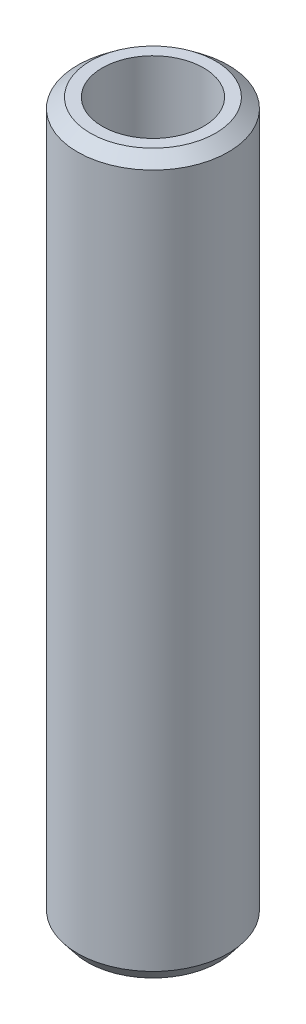
SolidWorks part; units mm, degrees
ref_plane "Front Plane" through (0, 0, 0) normal (0, 0, 1) x (1, 0, 0)
ref_plane "Top Plane" through (0, 0, 0) normal (0, 1, 0) x (1, 0, 0)
ref_plane "Right Plane" through (0, 0, 0) normal (1, 0, 0) x (0, 0, -1)
sketch "Sketch1" plane through (0, 0, 0) normal (0, 1, 0) x (1, 0, 0)
  circle A0 centre (0, 0) radius 40
  dimension "SHAFT_OD" = 80
extrude "Boss-Extrude1" add sketch "Sketch1" along normal blind 380.4895
sketch "Sketch2" plane through (0, 0, 0) normal (0, 1, 0) x (1, 0, 0)
  circle A0 centre (0, 0) radius 26.9065
  dimension "BORE_D" = 53.813
extrude "Cut-Extrude1" cut sketch "Sketch2" along normal through all
chamfer "Chamfer1" distance 5.2922 angle 51.99 2 edges at (0, 380.4895, 40) (0, 0, 40) first distance on face at (0, 380.4895, 40) first distance on face at (0, 0, 26.9065)
